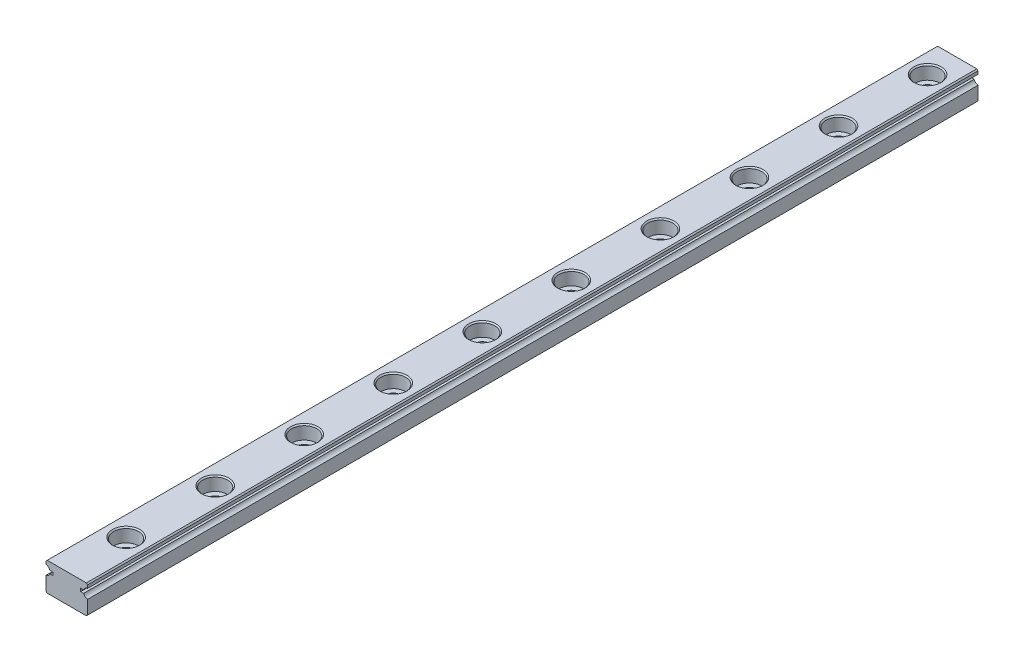
SolidWorks part; units mm, degrees
ref_plane "Спереди" through (0, 0, 0) normal (0, 0, 1) x (1, 0, 0)
ref_plane "Сверху" through (0, 0, 0) normal (0, 1, 0) x (1, 0, 0)
ref_plane "Справа" through (0, 0, 0) normal (1, 0, 0) x (0, 0, -1)
sketch "Sketch1" plane through (0, 0, 0) normal (0, 0, 1) x (1, 0, 0)
  line L0 (0, 0) -> (0, 4.3706) construction
  line L1 (-3.3, -2.4) -> (3.3, -2.4)
  line L2 (-3.5, -2.2) -> (-3.5, 0.1063)
  line L3 (-3.3, 2.4) -> (3.3, 2.4)
  line L4 (3.5, -2.2) -> (3.5, 0.1063)
  line L5 (-3.5, -2.4) -> (3.5, 2.4) construction
  line L6 (-3.5, 2.4) -> (3.5, -2.4) construction
  line L7 (-3.5, 1.6937) -> (-3.5, 2.2)
  line L8 (3.5, 1.6937) -> (3.5, 2.2)
  line L9 (-3.5, -2.2) -> (-3.3, -2.4)
  line L10 (3.3, -2.4) -> (3.5, -2.2)
  line L11 (3.3, 2.4) -> (3.5, 2.2)
  line L12 (-3.5, 2.2) -> (-3.3, 2.4)
  line L13 (2.8401, 0.65) -> (2.3401, 0.65)
  line L14 (-2.8401, 0.65) -> (-2.3401, 0.65)
  line L15 (2.3401, 0.65) -> (2.3401, 1.15)
  line L16 (-2.8401, 1.15) -> (-2.3401, 1.15)
  line L17 (-2.3401, 0.65) -> (-2.3401, 1.15)
  line L18 (2.8401, 1.15) -> (2.3401, 1.15)
  arc A0 (-3.5, 1.6937) -> (-2.8401, 1.15) centre (-3.6, 0.9) cw
  arc A1 (3.5, 1.6937) -> (2.8401, 1.15) centre (3.6, 0.9) ccw
  arc A2 (-2.8401, 0.65) -> (-3.5, 0.1063) centre (-3.6, 0.9) cw
  arc A3 (2.8401, 0.65) -> (3.5, 0.1063) centre (3.6, 0.9) ccw
  point P0 (0, 0)
  dimension "D4" = 0.8
  dimension "D5" = 0.1
  dimension "D1" = 7
  dimension "D2" = 4.8
  dimension "D3" = 1.5
  dimension "D6" = 0.5
  dimension "D7" = 0.5
extrude "Extrude1" add sketch "Sketch1" along normal blind 150
sketch "Sketch2" plane through (0, 2.4, 0) normal (0, 1, 0) x (1, 0, 0)
  line L0 (0, 0) -> (0, -5) construction
  circle A0 centre (0, -5) radius 1.2
  circle A1 centre (0, -5) radius 2.1
  dimension "D1" = 2.4
  dimension "D2" = 4.2
  dimension "D3" = 5
extrude "Extrude2" cut sketch "Sketch2" against normal up to next contours A0 region at (0, 2.4, 5)
extrude "Extrude4" cut sketch "Sketch" against normal blind 2.3
sketch "Sketch" plane through (0, 2.4, 0) normal (0, 1, 0) x (1, 0, 0) same geometry as "Sketch2"
chamfer "Chamfer1" distance 0.2 angle 45 2 edges at (0, -2.4, 6.2) (0, 2.4, 7.1)
pattern_linear "LPattern1" count 10 spacing 15 along (0, 0, 1) of "Extrude4", "Chamfer1", "Extrude2"
